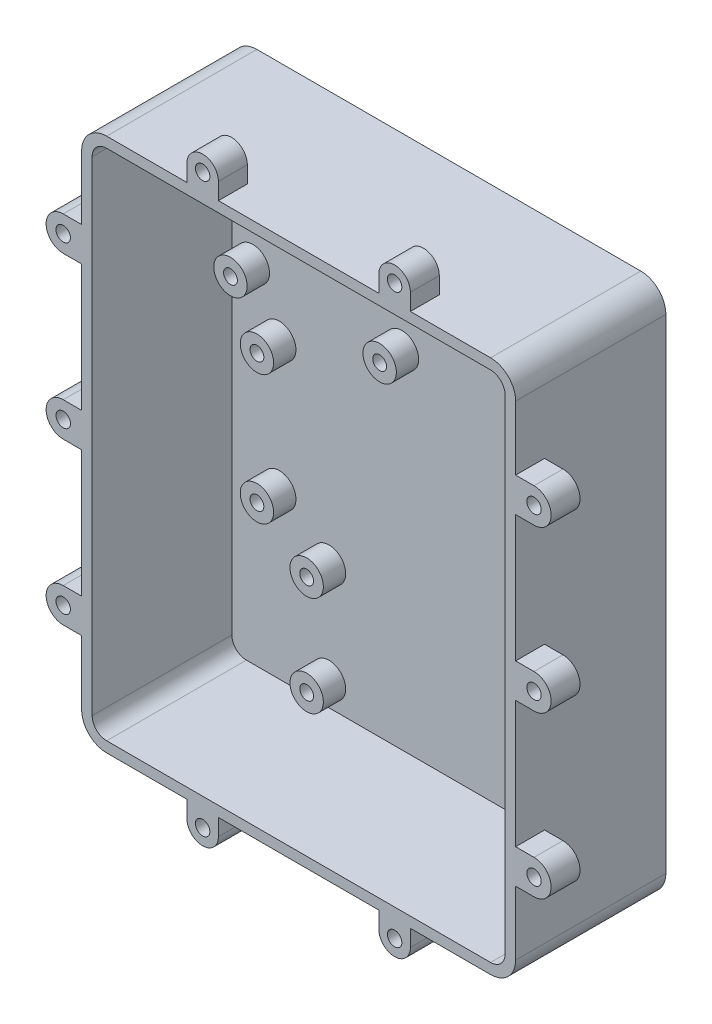
SolidWorks part; units mm, degrees
material "ABS"
ref_plane "X-Y Datum" through (0, 0, 0) normal (0, 0, 1) x (1, 0, 0)
ref_plane "X-Z Datum" through (0, 0, 0) normal (0, 1, 0) x (1, 0, 0)
ref_plane "Y-Z Datum" through (0, 0, 0) normal (1, 0, 0) x (0, 0, -1)
sketch "Sketch1" plane through (0, 0, 0) normal (0, 0, 1) x (1, 0, 0)
  line L1 (-82.55, 101.6) -> (82.55, 101.6)
  line L2 (-82.55, 101.6) -> (-82.55, -101.6)
  line L3 (-82.55, -101.6) -> (82.55, -101.6)
  line L4 (82.55, 101.6) -> (82.55, -101.6)
  line L5 (-82.55, 101.6) -> (82.55, -101.6) construction
  line L6 (-82.55, -101.6) -> (82.55, 101.6) construction
  point P0 (0, 0)
  dimension "D1" = 165.1
  dimension "D2" = 203.2
extrude "Boss-Extrude1" add sketch "Sketch1" along normal blind 57.15
fillet "Fillet1" radius 9.525 4 edges at (82.55, 101.6, 28.575) (-82.55, 101.6, 28.575) (-82.55, -101.6, 28.575) (82.55, -101.6, 28.575)
shell "Shell1" thickness 4 removed face at (0, 0, 57.15)
sketch "Sketch2" plane through (0, 0, 4) normal (0, 0, 1) x (1, 0, 0)
  line L0 (0, -97.6) -> (0, 97.6) construction
  line L1 (-73.025, -97.6) -> (73.025, -97.6) construction
  line L2 (73.025, 97.6) -> (-73.025, 97.6) construction
  line L3 (-78.55, 92.075) -> (-78.55, -92.075) construction
  line L4 (-44.45, -47.308) -> (44.45, -47.308) construction
  line L5 (-44.45, -47.308) -> (-44.45, -91.25) construction
  line L6 (-44.45, -91.25) -> (44.45, -91.25) construction
  line L7 (44.45, -47.308) -> (44.45, -91.25) construction
  line L8 (-44.45, -47.308) -> (44.45, -91.25) construction
  line L9 (-44.45, -91.25) -> (44.45, -47.308) construction
  line L10 (-41.6, -50.279) -> (41.6, -50.279) construction
  line L11 (-41.6, -50.279) -> (-41.6, -88.279) construction
  line L12 (-41.6, -88.279) -> (41.6, -88.279) construction
  line L13 (41.6, -50.279) -> (41.6, -88.279) construction
  line L14 (-41.6, -50.279) -> (41.6, -88.279) construction
  line L15 (-41.6, -88.279) -> (41.6, -50.279) construction
  line L16 (-78.55, 92.075) -> (-78.55, -92.075)
  line L17 (73.025, 97.6) -> (-73.025, 97.6) construction
  line L18 (-60.516, 14.011) -> (61.1507, 14.011) construction
  line L19 (-60.516, 14.011) -> (-60.516, -35.221) construction
  line L20 (-60.516, -35.221) -> (61.1507, -35.221) construction
  line L21 (61.1507, 14.011) -> (61.1507, -35.221) construction
  line L22 (-60.516, 14.011) -> (61.1507, -35.221) construction
  line L23 (-60.516, -35.221) -> (61.1507, 14.011) construction
  line L24 (-70.58, 84.245) -> (59.42, 84.245) construction
  line L25 (-70.58, 84.245) -> (-70.58, 34.245) construction
  line L26 (-70.58, 34.245) -> (59.42, 34.245) construction
  line L27 (59.42, 84.245) -> (59.42, 34.245) construction
  line L28 (-70.58, 84.245) -> (59.42, 34.245) construction
  line L29 (-70.58, 34.245) -> (59.42, 84.245) construction
  line L30 (-72.0727, 19.748) -> (72.7073, 19.748) construction
  line L31 (-72.0727, 19.748) -> (-72.0727, -40.958) construction
  line L32 (-72.0727, -40.958) -> (72.7073, -40.958) construction
  line L33 (72.7073, 19.748) -> (72.7073, -40.958) construction
  line L34 (-72.0727, 19.748) -> (72.7073, -40.958) construction
  line L35 (-72.0727, -40.958) -> (72.7073, 19.748) construction
  line L36 (-72.255, 89.217) -> (61.095, 89.217) construction
  line L37 (-72.255, 89.217) -> (-72.255, 29.273) construction
  line L38 (-72.255, 29.273) -> (61.095, 29.273) construction
  line L39 (61.095, 89.217) -> (61.095, 29.273) construction
  line L40 (-72.255, 89.217) -> (61.095, 29.273) construction
  line L41 (-72.255, 29.273) -> (61.095, 89.217) construction
  line L42 (-44.8662, 59.245) -> (33.7062, 59.245) construction
  circle A1 centre (-41.6, -88.279) radius 6.35
  circle A2 centre (41.6, -88.279) radius 6.35
  circle A3 centre (41.6, -50.279) radius 6.35
  circle A4 centre (-41.6, -50.279) radius 6.35
  circle A5 centre (-60.516, -35.221) radius 6.35
  circle A6 centre (61.1507, -35.221) radius 6.35
  circle A7 centre (61.1507, 14.011) radius 6.35
  circle A8 centre (-60.516, 14.011) radius 6.35
  circle A9 centre (-70.58, 34.245) radius 6.35
  circle A10 centre (59.42, 34.245) radius 6.35
  circle A11 centre (-70.58, 84.245) radius 6.35
  circle A12 centre (59.42, 84.245) radius 6.35
  circle A13 centre (-13.83, 34.245) radius 6.35
  circle A14 centre (-13.83, 84.245) radius 6.35
  point P6 (0, -69.279)
  point P11 (0, -69.279)
  point P18 (0.3173, -10.605)
  point P23 (-5.58, 59.245)
  point P28 (-5.58, 59.245)
  point P29 (0.3173, -10.605)
  point P57 (-5.58, 59.245)
  dimension "D22" = 12.7
  dimension "D1" = 43.942
  dimension "D2" = 88.9
  dimension "D3" = 83.2
  dimension "D4" = 38
  dimension "D5" = 18.034
  dimension "D6" = 121.6667
  dimension "D7" = 49.232
  dimension "D8" = 7.97
  dimension "D9" = 130
  dimension "D10" = 50
  dimension "D11" = 6.35
  dimension "D12" = 144.78
  dimension "D13" = 60.706
  dimension "D14" = 59.944
  dimension "D15" = 133.35
  dimension "D16" = 6.35
  dimension "D17" = 9.525
  dimension "D18" = 8.383
  dimension "D20" = 56.75
extrude "Boss-Extrude2" add sketch "Sketch2" along normal blind 8.5 contours A4 | A1 | A2 | A3 region at (-41.6, -88.279, 4) region at (41.6, -88.279, 4) region at (41.6, -50.279, 4) region at (-41.6, -50.279, 4)
sketch "Sketch3" plane through (0, 0, 12.5) normal (0, 0, 1) x (1, 0, 0)
  circle A0 centre (-41.6, -88.279) radius 2.625
  circle A1 centre (41.6, -88.279) radius 2.625
  circle A2 centre (41.6, -50.279) radius 2.625
  circle A4 centre (-41.6, -50.279) radius 2.625
extrude "Cut-Extrude1" cut sketch "Sketch3" against normal blind 5 contours A4 | A0 | A1 | A2 region at (-41.6, -88.279, 12.5) region at (41.6, -88.279, 12.5) region at (41.6, -50.279, 12.5) region at (-41.6, -50.279, 12.5)
extrude "Boss-Extrude6" add sketch "Sketch2<3>" along normal blind 8.5 contours A5 | A8 | A6 | A7 | A13 | A9 | A11 | A14 | A12 | A10 region at (-60.516, -35.221, 4) region at (61.1507, -35.221, 4) region at (61.1507, 14.011, 4) region at (-60.516, 14.011, 4) region at (-70.58, 34.245, 4) region at (59.42, 34.245, 4) region at (-70.58, 84.245, 4) region at (59.42, 84.245, 4) region at (-13.83, 34.245, 4) region at (-13.83, 84.245, 4)
sketch "Sketch2<3>" plane through (0, 0, 4) normal (0, 0, 1) x (1, 0, 0) same geometry as "Sketch2"
sketch "Sketch13" plane through (0, 0, 12.5) normal (0, 0, 1) x (1, 0, 0)
  circle A0 centre (-60.516, -35.221) radius 2.625
  circle A1 centre (61.1507, -35.221) radius 2.625
  circle A2 centre (61.1507, 14.011) radius 2.625
  circle A3 centre (-60.516, 14.011) radius 2.625
  circle A4 centre (-13.83, 34.245) radius 2.625
  circle A5 centre (-70.58, 34.245) radius 2.625
  circle A6 centre (59.42, 34.245) radius 2.625
  circle A7 centre (59.42, 84.245) radius 2.625
  circle A8 centre (-13.83, 84.245) radius 2.625
  circle A9 centre (-70.58, 84.245) radius 2.625
extrude "Cut-Extrude5" cut sketch "Sketch13" against normal blind 7
sketch "Sketch4" plane through (0, 0, 57.15) normal (0, 0, 1) x (1, 0, 0)
  line L0 (-82.55, 92.075) -> (-82.55, -92.075) construction
  line L1 (-73.025, -101.6) -> (73.025, -101.6) construction
  line L2 (-82.55, 92.075) -> (-82.55, -92.075)
  line L3 (-73.025, -101.6) -> (73.025, -101.6)
  line L4 (-82.55, 0) -> (-89.55, 0) construction
  line L5 (-89.55, 6.5) -> (-82.55, 6.5)
  line L6 (-89.55, -6.5) -> (-82.55, -6.5)
  line L7 (-73.025, -101.6) -> (0, -101.6)
  line L8 (-36.5125, -101.6) -> (-36.5125, -108.6) construction
  line L9 (0, -101.6) -> (0, -117.385) construction
  line L10 (-30.0125, -108.6) -> (-30.0125, -101.6)
  line L11 (-43.0125, -108.6) -> (-43.0125, -101.6)
  line L12 (30.0125, -108.6) -> (30.0125, -101.6)
  line L13 (36.5125, -101.6) -> (36.5125, -108.6) construction
  line L14 (43.0125, -108.6) -> (43.0125, -101.6)
  circle A0 centre (-89.55, 0) radius 2.75
  circle A1 centre (-89.55, 0) radius 6.5
  circle A2 centre (-36.5125, -108.6) radius 6.5
  circle A3 centre (-36.5125, -108.6) radius 2.75
  circle A4 centre (36.5125, -108.6) radius 2.75
  circle A5 centre (36.5125, -108.6) radius 6.5
  point P13 (0, -101.6)
  dimension "D1" = 5.5
  dimension "D2" = 13
  dimension "D3" = 7
  dimension "D4" = 146.05
  dimension "D5" = 73.025
extrude "Boss-Extrude3" add sketch "Sketch4" against normal blind 11 contours A1 L6 L2 L5 | A1 | A0 region at (-82.6976, 0, 57.15) region at (-85.0838, 4.4662, 57.15) region at (-89.55, 0, 57.15)
extrude "Cut-Extrude2" cut sketch "Sketch4<6>" against normal blind 8 and the other way through all contours A0 region at (-89.55, 0, 57.15)
sketch "Sketch4<6>" plane through (0, 0, 57.15) normal (0, 0, 1) x (1, 0, 0) same geometry as "Sketch4"
pattern_linear "LPattern1" count 2 spacing 61.214 along (0, 1, 0) count 2 spacing 61.214 along (0, -1, 0) of "Boss-Extrude3", "Cut-Extrude2"
mirror "Mirror1" about plane through (0, 0, 0) normal (1, 0, 0) of "LPattern1"
sketch "Sketch12" plane through (0, 0, 57.15) normal (0, 0, 1) x (1, 0, 0)
  line L0 (-73.025, -101.6) -> (73.025, -101.6) construction
  line L1 (-73.025, -101.6) -> (73.025, -101.6)
  line L2 (0, -101.6) -> (0, -113.5544) construction
  line L3 (-73.025, -101.6) -> (0, -101.6)
  line L4 (0, -101.6) -> (-36.5125, -101.6)
  line L5 (-36.5125, -101.6) -> (-36.5125, -107.95) construction
  line L6 (-42.5125, -107.95) -> (-42.5125, -101.6)
  line L7 (-30.5125, -107.95) -> (-30.5125, -101.6)
  line L8 (30.5125, -107.95) -> (30.5125, -101.6)
  line L9 (36.5125, -101.6) -> (36.5125, -107.95) construction
  line L10 (42.5125, -107.95) -> (42.5125, -101.6)
  circle A0 centre (-36.5125, -107.95) radius 6
  circle A1 centre (-36.5125, -107.95) radius 2.75
  circle A2 centre (36.5125, -107.95) radius 6
  circle A3 centre (36.5125, -107.95) radius 2.75
  line M16 (-73.025, -101.6) -> (73.025, -101.6)
  dimension "D1" = 12
  dimension "D2" = 5.5
  dimension "D3" = 6.35
extrude "Boss-Extrude5" add sketch "Sketch12" against normal blind 11 contours A0 A1 | A0 L7 L3 L6 | L8 A2 L10 M16 | A2 A3 | A3 | A1 region at (36.5125, -101.7358, 57.15) region at (-39.5125, -101.7358, 57.15) region at (-36.5125, -102.1197, 57.15) region at (36.5125, -102.1197, 57.15) region at (-36.5125, -107.95, 57.15) region at (36.5125, -107.95, 57.15)
extrude "Cut-Extrude3" cut sketch "Sketch12<3>" against normal blind 8 contours A1 | A3 region at (-36.5125, -107.95, 57.15) region at (36.5125, -107.95, 57.15)
sketch "Sketch12<3>" plane through (0, 0, 57.15) normal (0, 0, 1) x (1, 0, 0) same geometry as "Sketch12"
mirror "Mirror2" about plane through (0, 0, 0) normal (0, 1, 0) of "Cut-Extrude3", "Boss-Extrude5"
